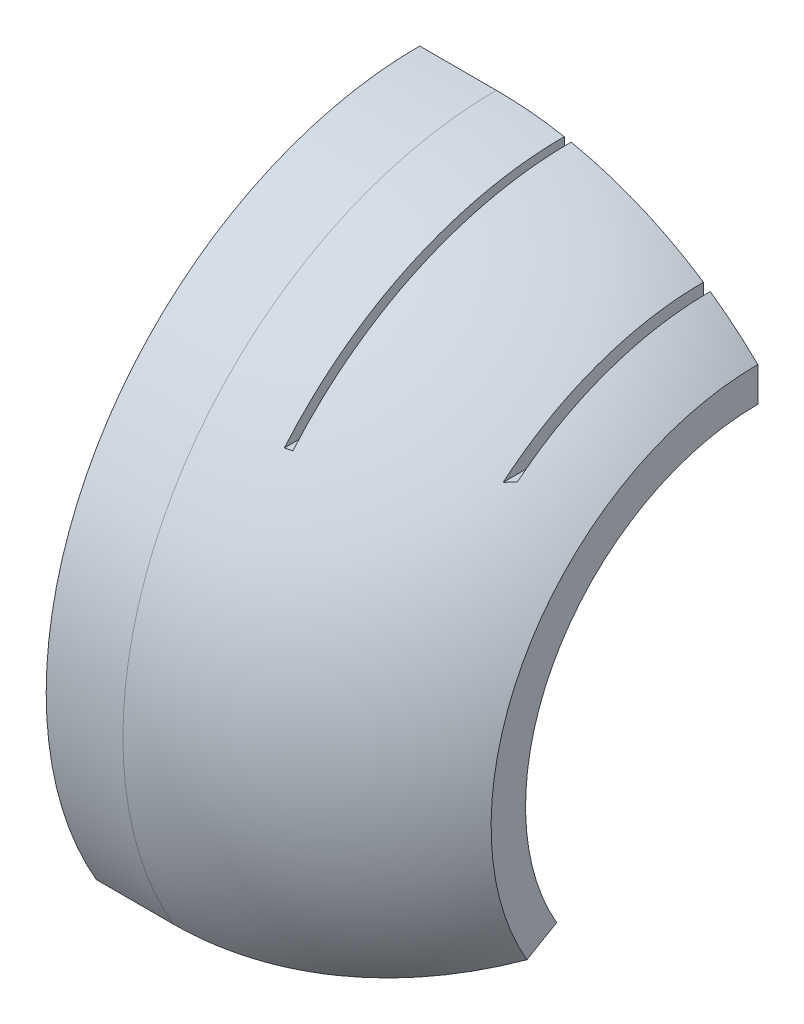
SolidWorks part; units mm, degrees
material "铸造合金钢"
ref_plane "前视基准面" through (0, 0, 0) normal (0, 0, 1) x (1, 0, 0)
ref_plane "上视基准面" through (0, 0, 0) normal (0, 1, 0) x (1, 0, 0)
ref_plane "右视基准面" through (0, 0, 0) normal (1, 0, 0) x (0, 0, -1)
sketch "草图1" plane through (0, 0, 0) normal (0, 0, 1) x (1, 0, 0)
  line L0 (0, 0) -> (0, 31.2525) construction
  line L1 (0, 55) -> (0, 51.5)
  line L2 (0, -51.5) -> (0, -55)
  arc A0 (0, 55) -> (0, -55) centre (0, 0) ccw
  arc A1 (0, 51.5) -> (0, -51.5) centre (0, 0) ccw
  dimension "D1" = 110
  dimension "D2" = 103
revolve "旋转8" add sketch "草图1" angle 360 about L0
sketch "草图2" plane through (0, 0, 0) normal (0, 0, 1) x (1, 0, 0)
  line L0 (0, 55) -> (0, -55)
  line L1 (0, -55) -> (55, -55)
  line L2 (55, -55) -> (55, 55)
  line L3 (55, 55) -> (0, 55)
  circle A0 centre (0, 0) radius 55 construction
extrude "切除-拉伸1" cut sketch "草图2" against normal through all both and the other way through all
sketch "草图3" plane through (0, 0, 0) normal (0, 0, 1) x (1, 0, 0)
  line L0 (0, 55) -> (-38.5, 55)
  line L1 (-38.5, 55) -> (-38.5, -55)
  line L2 (-38.5, -55) -> (0, -55)
  line L3 (0, -55) -> (0, 55) construction
  line L4 (-38.5, 55) -> (-61.7731, 55)
  line L5 (-61.7731, 55) -> (-61.7731, -55)
  line L6 (-61.7731, -55) -> (-38.5, -55)
  arc A0 (0, 55) -> (0, -55) centre (0, 0) ccw construction
  dimension "D1" = 38.5
extrude "切除-拉伸2" cut sketch "草图3" against normal through all both and the other way through all contours L5 L6 L1 L4 region at (-50.1366, 0, 0)
sketch "草图4" plane through (-38.5, 0, 0) normal (-1, 0, 0) x (0, 0, 1)
  line L0 (0, 0) -> (0, 64.5299)
  line L1 (0, 0) -> (55.8845, -32.2649)
  arc A0 (0, 64.5299) -> (55.8845, -32.2649) centre (0, 0) ccw
  dimension "D1" = 120
extrude "切除-拉伸3" cut sketch "草图4" against normal through all
sketch "草图5" plane through (0, 0, 0) normal (0, 0, -1) x (-1, 0, 0)
  line L0 (30.5, 55) -> (30.5, 35)
  line L1 (30.5, 55) -> (31.5, 55)
  line L2 (31.5, 55) -> (31.5, 35)
  line L3 (31.5, 35) -> (30.5, 35)
  line L4 (38.5, -17.1026) -> (38.5, 34.2053) construction
  line L5 (0, 55) -> (49.1042, 55) construction
  line L6 (0, 51.5) -> (0, -25.75) construction
  line L8 (10, 35) -> (10, 55)
  line L9 (10, 55) -> (11, 55)
  line L10 (11, 55) -> (11, 35)
  line L11 (11, 35) -> (10, 35)
  dimension "D1" = 8
  dimension "D2" = 1
  dimension "D3" = 20
  dimension "D4" = 11
  dimension "D5" = 1
extrude "切除-拉伸4" cut sketch "草图5" against normal through all
sketch "草图6" plane through (0, 0, 0) normal (0, 0, 1) x (1, 0, 0)
  line L0 (0, 55) -> (11.3, 55)
  line L1 (11.3, 55) -> (11.3, 51.5)
  line L2 (11.3, 51.5) -> (0, 51.5)
  line L3 (0, -27.5) -> (0, 55) construction
  line L4 (0, 51.5) -> (0, 55)
  line L5 (0, 0) -> (14.7554, 0) construction
  dimension "D1" = 3.5
  dimension "D2" = 11.3
revolve "旋转9" add sketch "草图6" angle 360 about L5
sketch "草图7" plane through (0, 0, 0) normal (-1, 0, 0) x (0, 0, 1)
  line L0 (0, 55) -> (0, 0)
  line L1 (0, 0) -> (47.6314, -27.5)
  arc A0 (0, 55) -> (47.6314, -27.5) centre (0, 0) ccw
extrude "切除-拉伸5" cut sketch "草图7" against normal blind 10
mirror "镜向1" about plane through (11.3, 55, 0) normal (-1, 0, 0) of bodies 112
sketch "草图8" plane through (0, 0, 0) normal (0, 0, 1) x (1, 0, 0)
  line L0 (-38.5, 9.8195) -> (61.1, 9.8195)
  line L1 (-38.5, 39.2779) -> (-38.5, -19.6389) construction
  line L2 (61.1, -19.6389) -> (61.1, 39.2779) construction
  line L3 (11.3, 9.8195) -> (11.3, 56.7049)
  line L4 (11.3, 56.7049) -> (-38.5, 54.8058)
  line L5 (-38.5, 54.8058) -> (-38.5, -31.4393)
  line L6 (-38.5, -31.4393) -> (11.3, -31.4393)
  line L7 (11.3, -31.4393) -> (11.3, 9.8195)
extrude "切除-拉伸7" cut sketch "草图8" along normal through all contours L4 L5 L0 L3 | L6 L7 L0 L5 region at (-13.4284, 32.7907, 0) region at (-13.6, -10.8099, 0)
sketch "草图9" plane through (0, 0, 0) normal (0, 0, 1) x (1, 0, 0)
  line L0 (11.3, 55) -> (11.3, 58.9118)
  line L1 (11.3, 58.9118) -> (4.5673, 58.9118)
  line L2 (4.5673, 58.9118) -> (4.5673, -60.8482)
  line L3 (4.5673, -60.8482) -> (11.3, -60.8482)
  line L4 (11.3, -60.8482) -> (11.3, 55)
extrude "切除-拉伸8" cut sketch "草图9" against normal blind 70 and the other way blind 70
sketch "草图10" plane through (12.6, 0, 0) normal (1, 0, 0) x (0, 0, -1)
  line L0 (0, 55) -> (0, 0)
  line L1 (0, 0) -> (-47.6314, -27.5)
  arc A0 (-47.6314, -27.5) -> (0, 55) centre (0, 0) ccw
extrude "切除-拉伸9" cut sketch "草图10" against normal blind 70
